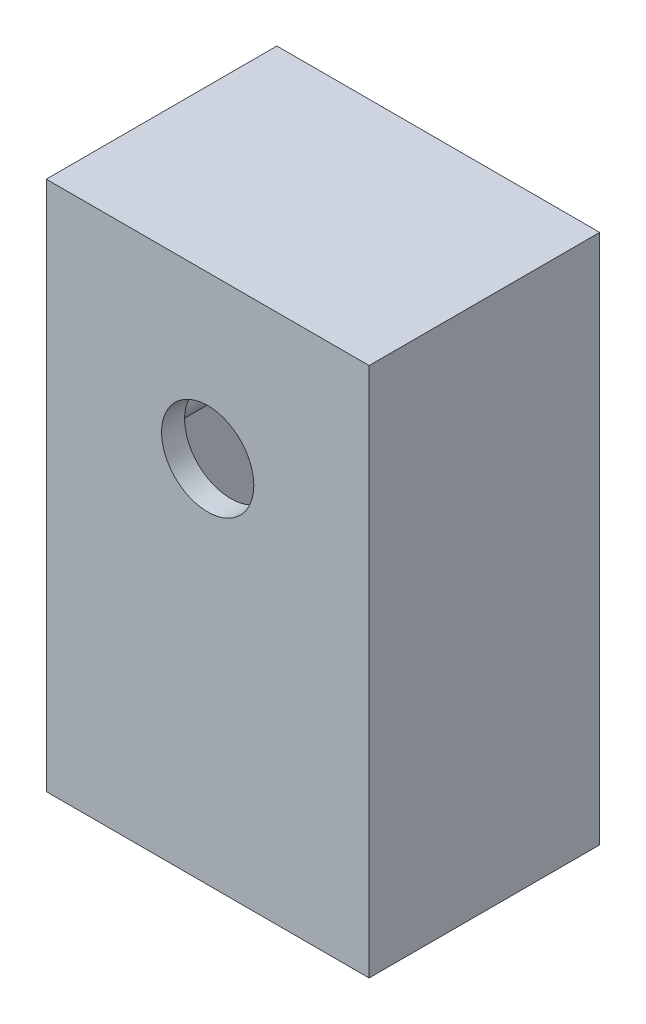
SolidWorks part; units mm, degrees
ref_plane "Alzado" through (0, 0, 0) normal (0, 0, 1) x (1, 0, 0)
ref_plane "Planta" through (0, 0, 0) normal (0, 1, 0) x (1, 0, 0)
ref_plane "Vista lateral" through (0, 0, 0) normal (1, 0, 0) x (0, 0, -1)
sketch "Croquis1" plane through (0, 0, 0) normal (0, 0, 1) x (1, 0, 0)
  line L0 (117743.4169, 152337.8366) -> (131743.4169, 152337.8366)
  line L1 (131743.4169, 152337.8366) -> (131743.4169, 161337.8366)
  line L2 (131743.4169, 161337.8366) -> (140743.4169, 161337.8366)
  line L3 (140743.4169, 161337.8366) -> (140743.4169, 175337.8366)
  line L4 (140743.4169, 175337.8366) -> (117743.4169, 175337.8366)
  line L5 (117743.4169, 175337.8366) -> (117743.4169, 152337.8366)
  line L6 (118743.4169, 152337.8366) -> (118743.4169, 166437.8366)
  line L7 (118743.4169, 174337.8366) -> (122843.4169, 174337.8366)
  line L8 (130743.4169, 152337.8366) -> (130743.4169, 162337.8366)
  line L9 (140743.4169, 162337.8366) -> (130743.4169, 162337.8366)
  line L10 (131743.4169, 161337.8366) -> (108743.4169, 161337.8366)
  line L11 (108743.4169, 161337.8366) -> (108743.4169, 162337.8366)
  line L12 (108743.4169, 162337.8366) -> (122843.4169, 162337.8366)
  line L13 (131743.4169, 161337.8366) -> (131743.4169, 184337.8366)
  line L14 (131743.4169, 184337.8366) -> (130743.4169, 184337.8366)
  line L15 (130743.4169, 184337.8366) -> (130743.4169, 170237.8366)
  line L16 (118743.4169, 174337.8366) -> (118743.4169, 184337.8366)
  line L17 (118743.4169, 184337.8366) -> (117743.4169, 184337.8366)
  line L18 (117743.4169, 184337.8366) -> (117743.4169, 175337.8366)
  line L19 (118743.4169, 174337.8366) -> (108743.4169, 174337.8366)
  line L20 (108743.4169, 174337.8366) -> (108743.4169, 175337.8366)
  line L21 (108743.4169, 175337.8366) -> (117743.4169, 175337.8366)
  line L22 (108743.4169, 174337.8366) -> (108743.4169, 162337.8366)
  line L23 (118743.4169, 184337.8366) -> (130743.4169, 184337.8366)
  line L24 (122743.4169, 174237.8366) -> (122743.4169, 172837.8366)
  line L25 (124243.4169, 171337.8366) -> (125243.4169, 171337.8366)
  line L26 (126743.4169, 172837.8366) -> (126743.4169, 174237.8366)
  line L27 (118843.4169, 170337.8366) -> (120243.4169, 170337.8366)
  line L28 (121743.4169, 168837.8366) -> (121743.4169, 167837.8366)
  line L29 (120243.4169, 166337.8366) -> (118843.4169, 166337.8366)
  line L30 (130643.4169, 170337.8366) -> (129243.4169, 170337.8366)
  line L31 (127743.4169, 168837.8366) -> (127743.4169, 167837.8366)
  line L32 (129243.4169, 166337.8366) -> (130643.4169, 166337.8366)
  line L33 (122743.4169, 162437.8366) -> (122743.4169, 163837.8366)
  line L34 (124243.4169, 165337.8366) -> (125243.4169, 165337.8366)
  line L35 (126743.4169, 163837.8366) -> (126743.4169, 162337.8366)
  line L36 (121743.4169, 168337.8366) -> (127743.4169, 168337.8366) construction
  line L37 (118743.4169, 170237.8366) -> (120243.4169, 170237.8366)
  line L38 (118843.4169, 174237.8366) -> (122743.4169, 174237.8366)
  line L39 (121643.4169, 168837.8366) -> (121643.4169, 167837.8366)
  line L40 (118843.4169, 162437.8366) -> (118843.4169, 166337.8366)
  line L41 (118843.4169, 162437.8366) -> (122743.4169, 162437.8366)
  line L42 (130643.4169, 174237.8366) -> (130643.4169, 170337.8366)
  line L43 (120243.4169, 166437.8366) -> (118743.4169, 166437.8366)
  line L44 (118743.4169, 174237.8366) -> (140743.4169, 174237.8366) construction
  line L45 (122843.4169, 162337.8366) -> (122843.4169, 163837.8366)
  line L46 (124243.4169, 165237.8366) -> (125243.4169, 165237.8366)
  line L47 (126643.4169, 163837.8366) -> (126643.4169, 162337.8366)
  line L48 (130743.4169, 170237.8366) -> (129243.4169, 170237.8366)
  line L49 (127843.4169, 168837.8366) -> (127843.4169, 167837.8366)
  line L50 (129243.4169, 166437.8366) -> (130743.4169, 166437.8366)
  line L51 (122843.4169, 174337.8366) -> (122843.4169, 172837.8366)
  line L52 (124243.4169, 171437.8366) -> (125243.4169, 171437.8366)
  line L53 (126643.4169, 172837.8366) -> (126643.4169, 174337.8366)
  line L54 (130643.4169, 166337.8366) -> (130643.4169, 162437.8366)
  line L55 (130743.4169, 166437.8366) -> (130743.4169, 162337.8366)
  line L56 (129243.4169, 166337.8366) -> (130743.4169, 166337.8366) construction
  line L57 (130743.4169, 170337.8366) -> (129243.4169, 170337.8366) construction
  line L58 (126643.4169, 174337.8366) -> (140743.4169, 174337.8366)
  line L59 (118743.4169, 174337.8366) -> (140743.4169, 174337.8366) construction
  line L60 (126743.4169, 174237.8366) -> (130643.4169, 174237.8366)
  line L61 (126743.4169, 172837.8366) -> (126743.4169, 174337.8366) construction
  line L62 (122743.4169, 174337.8366) -> (122743.4169, 172837.8366) construction
  line L63 (118743.4169, 170237.8366) -> (118743.4169, 174337.8366)
  line L64 (118843.4169, 170337.8366) -> (118843.4169, 174237.8366)
  line L65 (118743.4169, 170337.8366) -> (120243.4169, 170337.8366) construction
  line L66 (120243.4169, 166337.8366) -> (118743.4169, 166337.8366) construction
  line L67 (126743.4169, 162437.8366) -> (130643.4169, 162437.8366)
  line L68 (122743.4169, 162337.8366) -> (122743.4169, 163837.8366) construction
  line L69 (126643.4169, 162337.8366) -> (130743.4169, 162337.8366)
  arc A0 (125243.4169, 165337.8366) -> (126743.4169, 163837.8366) centre (125243.4169, 163837.8366) cw
  arc A1 (122743.4169, 163837.8366) -> (124243.4169, 165337.8366) centre (124243.4169, 163837.8366) cw
  arc A2 (127743.4169, 167837.8366) -> (129243.4169, 166337.8366) centre (129243.4169, 167837.8366) ccw
  arc A3 (129243.4169, 170337.8366) -> (127743.4169, 168837.8366) centre (129243.4169, 168837.8366) ccw
  arc A4 (125243.4169, 171337.8366) -> (126743.4169, 172837.8366) centre (125243.4169, 172837.8366) ccw
  arc A5 (122743.4169, 172837.8366) -> (124243.4169, 171337.8366) centre (124243.4169, 172837.8366) ccw
  arc A6 (120243.4169, 170337.8366) -> (121743.4169, 168837.8366) centre (120243.4169, 168837.8366) cw
  arc A7 (121743.4169, 167837.8366) -> (120243.4169, 166337.8366) centre (120243.4169, 167837.8366) cw
  circle A8 centre (124743.4169, 168337.8366) radius 2000
  arc A9 (120243.4169, 170237.8366) -> (121643.4169, 168837.8366) centre (120243.4169, 168837.8366) cw
  arc A10 (121643.4169, 167837.8366) -> (120243.4169, 166437.8366) centre (120243.4169, 167837.8366) cw
  arc A11 (122843.4169, 163837.8366) -> (124243.4169, 165237.8366) centre (124243.4169, 163837.8366) cw
  arc A12 (125243.4169, 165237.8366) -> (126643.4169, 163837.8366) centre (125243.4169, 163837.8366) cw
  arc A13 (129243.4169, 170237.8366) -> (127843.4169, 168837.8366) centre (129243.4169, 168837.8366) ccw
  arc A14 (127843.4169, 167837.8366) -> (129243.4169, 166437.8366) centre (129243.4169, 167837.8366) ccw
  arc A15 (122843.4169, 172837.8366) -> (124243.4169, 171437.8366) centre (124243.4169, 172837.8366) ccw
  arc A16 (125243.4169, 171437.8366) -> (126643.4169, 172837.8366) centre (125243.4169, 172837.8366) ccw
  circle A17 centre (124743.4169, 168337.8366) radius 1900
  point P34 (126743.4169, 163087.8366)
  point P39 (126743.4169, 165337.8366)
  point P42 (122743.4169, 165337.8366)
  point P45 (127743.4169, 166337.8366)
  point P48 (127743.4169, 170337.8366)
  point P51 (126743.4169, 171337.8366)
  point P54 (122743.4169, 171337.8366)
  point P57 (121743.4169, 170337.8366)
  point P60 (121743.4169, 166337.8366)
  dimension "D21" = 1500
  dimension "D22" = 4000
  dimension "D1" = 12000
  dimension "D2" = 1000
  dimension "D3" = 1000
  dimension "D4" = 1000
  dimension "D5" = 1000
  dimension "D6" = 12000
  dimension "D7" = 9000
  dimension "D8" = 9000
  dimension "D9" = 9000
  dimension "D10" = 9000
  dimension "D11" = 4000
  dimension "D12" = 4000
  dimension "D13" = 4000
  dimension "D14" = 4000
  dimension "D18" = 4000
  dimension "D19" = 4000
  dimension "D20" = 3000
  dimension "D23" = 100
  dimension "D24" = 100
  dimension "D25" = 100
  dimension "D26" = 100
ref_plane "Plano1" through (0, 161337.8366, 0) normal (0, 1, 0) x (1, 0, 0)
ref_plane "Plano2" through (0, 175337.8366, 0) normal (0, 1, 0) x (1, 0, 0)
ref_plane "Plano3" through (117743.4169, 0, 0) normal (1, 0, 0) x (0, 0, -1)
ref_plane "Plano4" through (131743.4169, 0, 0) normal (1, 0, 0) x (0, 0, -1)
ref_plane "Plano5" through (113243.4169, 0, 0) normal (1, 0, 0) x (0, 0, -1)
ref_plane "Plano6" through (0, 179837.8366, 0) normal (0, 1, 0) x (1, 0, 0)
ref_plane "Plano7" through (136243.4169, 0, 0) normal (1, 0, 0) x (0, 0, -1)
ref_plane "Plano8" through (0, 156837.8366, 0) normal (0, 1, 0) x (1, 0, 0)
sketch "Croquis2" plane through (0, 156837.8366, 0) normal (0, 1, 0) x (1, 0, 0)
  line L0 (117743.4169, 0) -> (131743.4169, 0) construction
  line L1 (117743.4169, 0) -> (131743.4169, 0)
  line L2 (131743.4169, 0) -> (131743.4169, 8000)
  line L3 (131743.4169, 8000) -> (130743.4169, 8000)
  line L4 (130743.4169, 8000) -> (130743.4169, 1000)
  line L5 (130743.4169, 1000) -> (118743.4169, 1000)
  line L6 (118743.4169, 1000) -> (118743.4169, 8000)
  line L7 (118743.4169, 8000) -> (117743.4169, 8000)
  line L8 (117743.4169, 8000) -> (117743.4169, 0)
  spline S0 degree 2 poles (130743.4169, 8000) (128761.6752, 7234.3483) (128743.4169, 1000) knots 0 0 0 0.590989 0.590989 0.590989
  spline S1 degree 2 poles (118743.4169, 8000) (120739.8111, 7120.5788) (120743.4169, 1000) knots 0 0 0 0.514461 0.514461 0.514461
  dimension "D1" = 1000
  dimension "D2" = 1000
  dimension "D3" = 1000
  dimension "D4" = 7000
  dimension "D5" = 7000
  dimension "D6" = 2000
  dimension "D7" = 2000
sketch "Croquis3" plane through (0, 179837.8366, 0) normal (0, 1, 0) x (1, 0, 0)
  line L0 (118743.4169, 1000) -> (118743.4169, 8000) construction
  line L1 (130743.4169, 1000) -> (118743.4169, 1000) construction
  line L2 (130743.4169, 8000) -> (130743.4169, 1000) construction
  line L3 (118743.4169, 1000) -> (118743.4169, 8000)
  line L4 (130743.4169, 1000) -> (118743.4169, 1000)
  line L5 (130743.4169, 8000) -> (130743.4169, 1000)
  parabola Q0 (118743.4169, 8000) -> (120743.4169, 1000) focus (118361.6774, 7241.9739) apex (118662.5082, 8033.1777) construction
  parabola Q1 (130743.4169, 8000) -> (128743.4169, 1000) focus (131040.6578, 7282.3326) apex (130778.3168, 8013.005) construction
  parabola Q2 (118743.4169, 8000) -> (120743.4169, 1000) focus (118361.6774, 7241.9739) apex (118662.5082, 8033.1777)
  parabola Q3 (130743.4169, 8000) -> (128743.4169, 1000) focus (131040.6578, 7282.3326) apex (130778.3168, 8013.005)
sketch "Croquis4" plane through (113243.4169, 0, 0) normal (1, 0, 0) x (0, 0, -1)
  line L0 (0, 174337.8366) -> (0, 162337.8366) construction
  line L1 (0, 174337.8366) -> (0, 162337.8366)
  line L2 (0, 162337.8366) -> (8000, 162337.8366)
  line L3 (0, 174337.8366) -> (8000, 174337.8366)
  spline S0 degree 2 poles (8000, 162337.8366) (6698.659, 164240.8241) (0, 164337.8366) knots 0 0 0 0.70753 0.70753 0.70753
  spline S1 degree 2 poles (8000, 174337.8366) (6599.8546, 172118.7435) (0, 172337.8366) knots 0 0 0 0.648378 0.648378 0.648378
  dimension "D1" = 8000
  dimension "D2" = 2000
  dimension "D3" = 2000
sketch "Croquis5" plane through (136243.4169, 0, 0) normal (1, 0, 0) x (0, 0, -1)
  line L0 (0, 162337.8366) -> (8000, 162337.8366) construction
  line L1 (0, 174337.8366) -> (0, 162337.8366) construction
  line L2 (0, 174337.8366) -> (8000, 174337.8366) construction
  line L3 (0, 162337.8366) -> (8000, 162337.8366)
  line L4 (0, 174337.8366) -> (0, 162337.8366)
  line L5 (0, 174337.8366) -> (8000, 174337.8366)
  parabola Q0 (8000, 162337.8366) -> (0, 164337.8366) focus (7402.6379, 161620.0634) apex (8222.0253, 161894.2353) construction
  parabola Q1 (8000, 174337.8366) -> (0, 172337.8366) focus (7073.338, 175098.4045) apex (8142.0414, 174597.2807) construction
  parabola Q2 (8000, 162337.8366) -> (0, 164337.8366) focus (7402.6379, 161620.0634) apex (8222.0253, 161894.2353)
  parabola Q3 (8000, 174337.8366) -> (0, 172337.8366) focus (7073.338, 175098.4045) apex (8142.0414, 174597.2807)
extrude "Saliente-Extruir1" add sketch "Croquis1" against normal blind 1000 contours L15 L58 L13 L4 | L19 L16 L4 L5 | L12 L5 L10 L6 | L6 L10 L5 L0 | L8 L10 L6 L0 | L1 L10 L8 L0 | L10 L13 L9 L8 | A12 L46 A11 L45 L12 L6 L10 L8 L69 L47 | L49 A14 L50 L55 L9 L13 L58 L15 L48 A13 | L52 A16 L53 L58 L15 L4 L16 L7 L51 A15 | A10 L39 A9 L37 L63 L19 L5 L12 L6 L43 | L28 A7 L29 L40 L41 L33 A1 L34 A0 L35 L67 L54 L32 A2 L31 A3 L30 L42 L60 L26 A4 L25 A5 L24 L38 L64 L27 A6 A8 | A16 L52 A15 L51 L7 L63 L37 A9 L39 A10 L43 L6 L12 L45 A11 L46 A12 L47 L69 L35 A0 L34 A1 L33 L41 L40 L29 A7 L28 A6 L27 L64 L38 L24 A5 L25 A4 L26 L60 L42 L30 A3 L31 A2 L32 L54 L67 L55 region at (118243.4169, 156837.8366, 0) region at (124743.4169, 156837.8366, 0) region at (118243.4169, 161837.8366, 0) region at (131243.4169, 156837.8366, 0) region at (124743.4169, 162689.636, 0) region at (119095.2163, 168337.8366, 0) region at (131243.4169, 161837.8366, 0) region at (126910.2941, 163137.8366, 0) region at (118760.3875, 164387.8366, 0) region at (118243.4169, 174837.8366, 0) region at (130391.6175, 168337.8366, 0) region at (124743.4169, 173986.0372, 0) region at (131243.4169, 174837.8366, 0)
extrude "Saliente-Extruir2" add sketch "Croquis1<6>" against normal blind 10000 contours L15 L58 L13 L4 | L19 L16 L4 L5 | L12 L5 L10 L6 | L6 L10 L5 L0 | L1 L10 L8 L0 | L10 L13 L9 L8 | L52 A16 L53 L58 L15 L4 L16 L7 L51 A15 | L49 A14 L50 L55 L9 L13 L58 L15 L48 A13 | A10 L39 A9 L37 L63 L19 L5 L12 L6 L43 region at (118243.4169, 156837.8366, 0) region at (118243.4169, 161837.8366, 0) region at (131243.4169, 156837.8366, 0) region at (119095.2163, 168337.8366, 0) region at (131243.4169, 161837.8366, 0) region at (118243.4169, 174837.8366, 0) region at (130391.6175, 168337.8366, 0) region at (124743.4169, 173986.0372, 0) region at (131243.4169, 174837.8366, 0)
sketch "Croquis1<6>" plane through (0, 0, 0) normal (0, 0, 1) x (1, 0, 0) same geometry as "Croquis1"
extrude "Saliente-Extruir3" add sketch "Croquis2" along normal blind 500 and the other way blind 500 contours L4 S0 L5 | S1 L6 L5 region at (119605.9639, 156837.8366, -3955.1574) region at (129880.6924, 156837.8366, -3967.5864)
